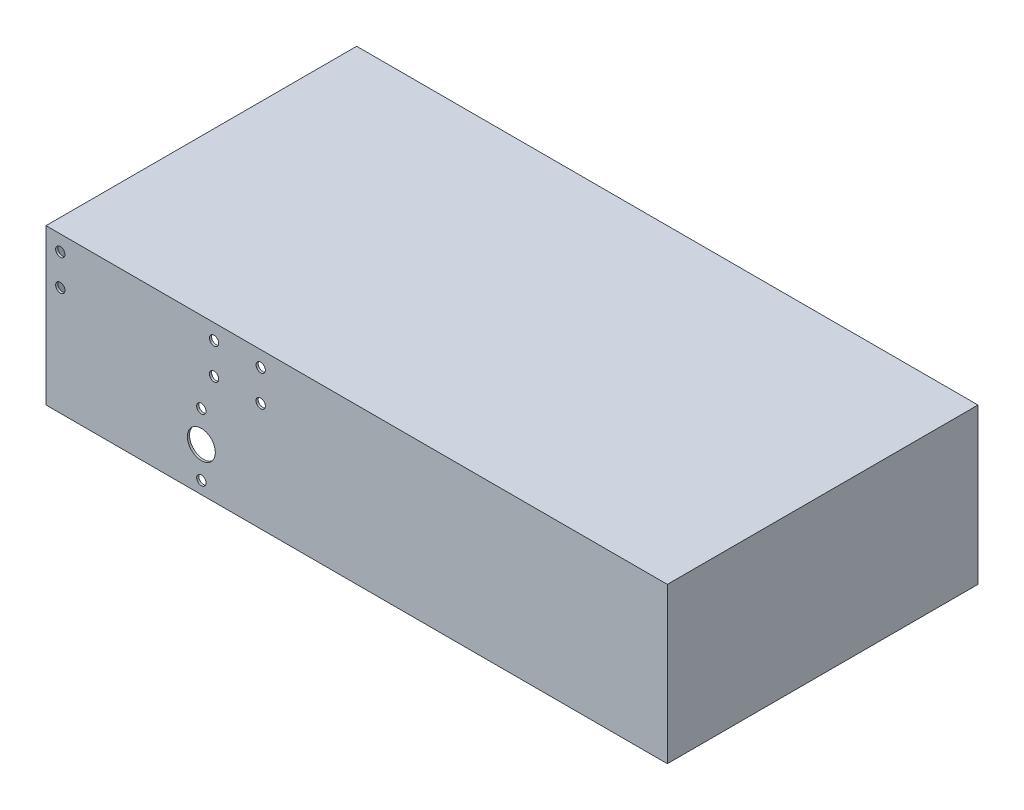
SolidWorks part; units mm, degrees
ref_plane "Front Plane" through (0, 0, 0) normal (0, 0, 1) x (1, 0, 0)
ref_plane "Top Plane" through (0, 0, 0) normal (0, 1, 0) x (1, 0, 0)
ref_plane "Right Plane" through (0, 0, 0) normal (1, 0, 0) x (0, 0, -1)
sketch "Sketch1" plane through (0, 0, 0) normal (0, 1, 0) x (1, 0, 0)
  line L1 (0, 50) -> (200, 50)
  line L2 (0, 50) -> (0, -50)
  line L3 (0, -50) -> (200, -50)
  line L4 (200, 50) -> (200, -50)
  point P4 (0, 0)
  dimension "D1" = 200
  dimension "D2" = 100
extrude "Boss-Extrude1" add sketch "Sketch1" along normal blind 50
sketch "Sketch2" plane through (0, 0, 50) normal (0, 0, 1) x (1, 0, 0)
  line L0 (0, 50) -> (0, 0) construction
  line L1 (50, 24) -> (50, 4) construction
  line L2 (0, 50) -> (200, 50) construction
  circle A0 centre (50, 14) radius 4.5
  circle A1 centre (50, 4) radius 1.5
  circle A2 centre (50, 24) radius 1.5
  point P0 (50, 14)
  point P9 (50, 14)
  point P12 (0, 0)
  dimension "D3" = 9
  dimension "D4" = 3
  dimension "D1" = 50
  dimension "D2" = 36
  dimension "D5" = 20
sketch "Sketch3" plane through (0, 0, 0) normal (0, -1, 0) x (1, 0, 0)
  line L0 (0.7, 49.3) -> (0.7, -49.3)
  line L1 (0.7, -49.3) -> (199.3, -49.3)
  line L2 (199.3, -49.3) -> (199.3, 49.3)
  line L3 (199.3, 49.3) -> (0.7, 49.3)
  line L4 (0, 50) -> (0, -50)
  line L5 (0, -50) -> (200, -50)
  line L6 (200, -50) -> (200, 50)
  line L7 (200, 50) -> (0, 50)
  line L8 (0, 50) -> (0, -50) construction
  line L9 (0, -50) -> (200, -50) construction
  line L10 (200, -50) -> (200, 50) construction
  line L11 (200, 50) -> (0, 50) construction
  dimension "D1" = 0
  dimension "D2" = 0.7
extrude "Cut-Extrude1" cut sketch "Sketch3" against normal offset from surface (49.3 mm away) 0.7 up to face at (100, 50, 0)
sketch "Sketch4" plane through (0, 0, 0) normal (0, -1, 0) x (1, 0, 0)
  line L0 (0.7, -49.3) -> (199.3, -49.3) construction
  line L1 (145, -49.3) -> (199.3, -49.3)
  line L2 (145, -49.3) -> (145, 49.3)
  line L3 (145, 49.3) -> (199.3, 49.3)
  line L4 (199.3, -49.3) -> (199.3, 49.3)
  line L5 (199.3, 49.3) -> (0.7, 49.3) construction
  line L6 (160, -47.9) -> (160, 49.3) construction
  line L7 (200, -50) -> (200, 50) construction
  line L8 (199.3, -49.3) -> (199.3, 49.3) construction
  circle A0 centre (160, 0.7) radius 11.43 construction
  point P12 (160, 0.7)
  point P18 (0, 0)
  point P19 (0, 0)
  point P20 (160, -23.5608)
  point P21 (160, 49.3)
  point P22 (160, -17.1532)
  point P23 (160, 49.3)
  point P24 (160, -19.0515)
  dimension "D3" = 22.86
  dimension "D1" = 40
  dimension "D2" = 55
  dimension "D4" = 50
extrude "Boss-Extrude2" add sketch "Sketch4" against normal blind 0.7
extrude "Cut-Extrude2" cut sketch "Sketch2" against normal through all
sketch "Sketch6" plane through (0, 0, 50) normal (0, 0, 1) x (1, 0, 0)
  line L0 (4.6, 50) -> (4.6, 0) construction
  line L1 (0, 50) -> (200, 50) construction
  line L2 (200, 0) -> (0, 0) construction
  line L3 (0, 45) -> (200, 45) construction
  line L4 (0, 50) -> (0, 0) construction
  line L5 (200, 50) -> (200, 0) construction
  line L6 (0, 35) -> (200, 35) construction
  line L7 (54.1, 45) -> (54.1, 35) construction
  line L8 (69.1, 45) -> (69.1, 35) construction
  circle A0 centre (4.6, 45) radius 1.5
  circle A1 centre (4.6, 35) radius 1.5
  circle A2 centre (54.1, 45) radius 1.5
  circle A3 centre (54.1, 35) radius 1.5
  circle A4 centre (69.1, 45) radius 1.5
  circle A5 centre (69.1, 35) radius 1.5
  point P27 (0, 35)
  dimension "D1" = 3
  dimension "D3" = 5
  dimension "D4" = 10
  dimension "D5" = 4.6
  dimension "D6" = 15
  dimension "D7" = 54.1
extrude "Cut-Extrude3" cut sketch "Sketch6" against normal up to surface (0.7 mm away) up to face at (51.5, 4, 49.3)
sketch "Sketch7" plane through (0, 0, 0) normal (-1, 0, 0) x (0, 0, 1)
  line L0 (42, 50) -> (42, 0) construction
  line L1 (-50, 50) -> (50, 50) construction
  line L2 (-50, 0) -> (50, 0) construction
  circle A0 centre (42, 45) radius 1.5
  circle A1 centre (42, 35) radius 1.5
  dimension "D4" = 3
  dimension "D1" = 8
  dimension "D2" = 5
  dimension "D3" = 10
extrude "Cut-Extrude4" cut sketch "Sketch7" against normal up to surface (0.7 mm away) up to face at (0.7, 24.65, 0)
